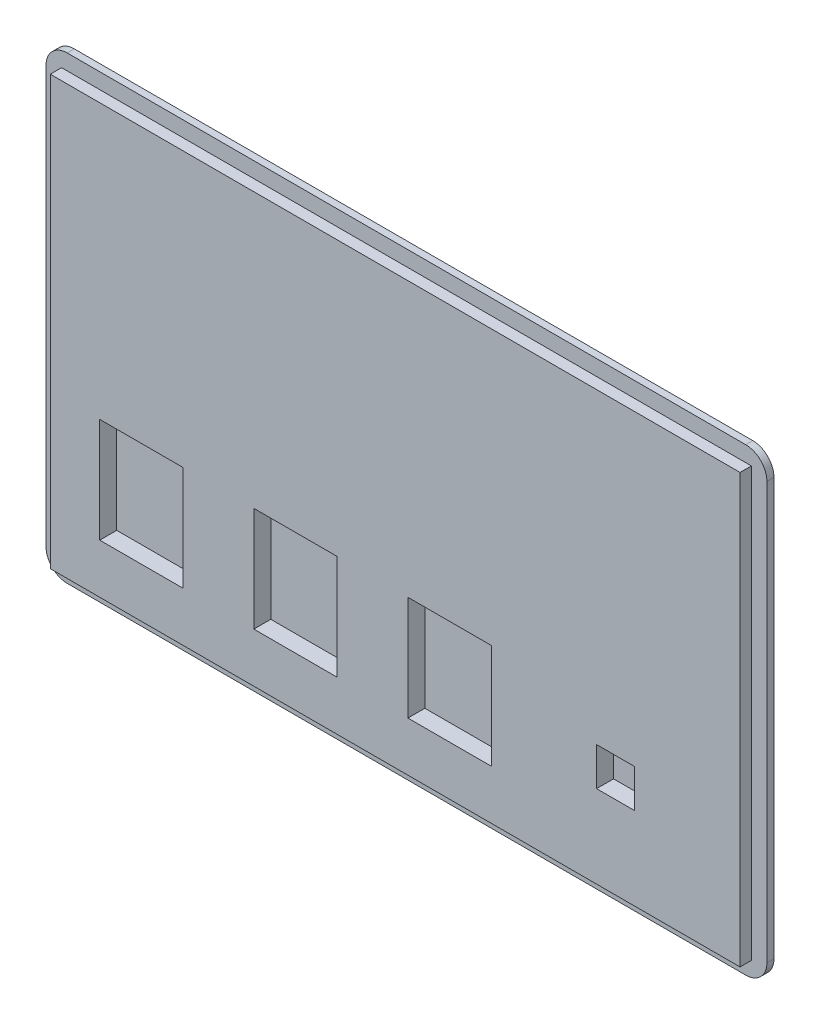
SolidWorks part; units mm, degrees
ref_plane "Přední rovina" through (0, 0, 0) normal (0, 0, 1) x (1, 0, 0)
ref_plane "Horní rovina" through (0, 0, 0) normal (0, 1, 0) x (1, 0, 0)
ref_plane "Pravá rovina" through (0, 0, 0) normal (1, 0, 0) x (0, 0, -1)
sketch "Skica1" plane through (0, 0, 0) normal (0, 0, 1) x (1, 0, 0)
  line L0 (64.6, 16.6) -> (52.8, 16.6) construction
  line L1 (0, 0) -> (102, 0)
  line L2 (0, 0) -> (0, 65)
  line L3 (0, 65) -> (102, 65)
  line L4 (102, 0) -> (102, 65)
  line L45 (2.2, 62.8) -> (99.8, 62.8)
  line L46 (2.2, 62.8) -> (2.2, 2.2)
  line L47 (2.2, 2.2) -> (99.8, 2.2)
  line L48 (99.8, 62.8) -> (99.8, 2.2)
  line L49 (9.2, 24) -> (21, 24)
  line L50 (9.2, 24) -> (9.2, 9.2)
  line L51 (9.2, 9.2) -> (21, 9.2)
  line L52 (21, 24) -> (21, 9.2)
  line L53 (31, 24) -> (42.8, 24)
  line L54 (31, 24) -> (31, 9.2)
  line L55 (31, 9.2) -> (42.8, 9.2)
  line L56 (42.8, 24) -> (42.8, 9.2)
  line L57 (52.8, 24) -> (64.6, 24)
  line L58 (52.8, 24) -> (52.8, 9.2)
  line L59 (52.8, 9.2) -> (64.6, 9.2)
  line L60 (64.6, 24) -> (64.6, 9.2)
  line L63 (79.5, 13.9) -> (84.9, 13.9)
  line L65 (79.5, 13.9) -> (79.5, 19.3)
  line L66 (79.5, 19.3) -> (84.9, 19.3)
  line L67 (84.9, 13.9) -> (84.9, 19.3)
  dimension "D4" = 14.9
  dimension "D15" = 102
  dimension "D18" = 65
  dimension "D20" = 2.2
  dimension "D21" = 2.2
  dimension "D22" = 2.2
  dimension "D23" = 2.2
  dimension "D25" = 11.8
  dimension "D26" = 14.8
  dimension "D27" = 11.8
  dimension "D28" = 11.8
  dimension "D32" = 7
  dimension "D33" = 7
  dimension "D34" = 10
  dimension "D35" = 10
  dimension "D36" = 5.4
  dimension "D37" = 5.4
  dimension "D39" = 97.6
extrude "Přidat vysunutím1" add sketch "Skica1" along normal blind 2.6 contours L48 L45 L46 L47 L49 L52 L51 L50 L53 L56 L55 L54 L57 L60 L59 L58 region at (52.2082, 34.1402, 0)
extrude "Přidat vysunutím2" add sketch "Skica1<3>" along normal blind 1 contours L1 L4 L3 L2 L45 L48 L47 L46 region at (1.2095, 32.5, 0)
sketch "Skica1<3>" plane through (0, 0, 0) normal (0, 0, 1) x (1, 0, 0) same geometry as "Skica1"
extrude "Přidat vysunutím3" add sketch "Skica1<5>" along normal blind 0.2 contours L58 L59 L60 | L54 L55 L56 | L52 L50 L51 | L67 L63 L65 L66 | L0 L60 L57 L58 | L65 L63 L67 L66 region at (58.7, 12.9, 0) region at (58.7, 20.3, 0) region at (52.2082, 34.1402, 0) region at (15.1, 16.6, 0) region at (36.9, 16.6, 0)
sketch "Skica1<5>" plane through (0, 0, 0) normal (0, 0, 1) x (1, 0, 0) same geometry as "Skica1"
fillet "Zaoblit1" radius 3 4 edges at (102, 65, 0.5) (0, 65, 0.5) (0, 0, 0.5) (102, 0, 0.5)
